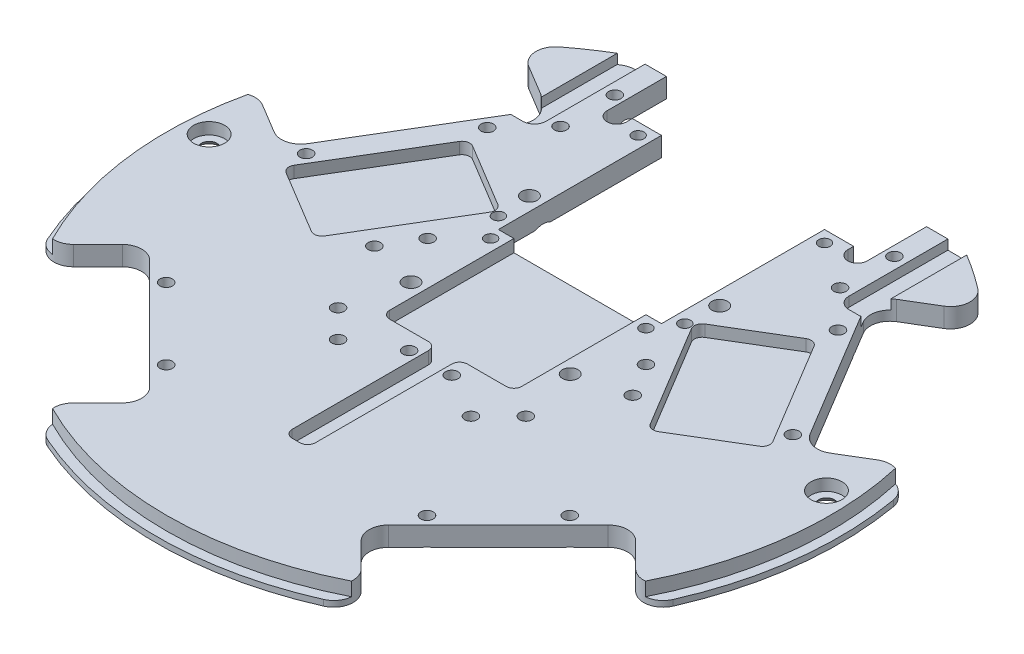
SolidWorks part; units mm, degrees
material "7079 Alloy"
ref_plane "Front" through (0, 0, 0) normal (0, 0, 1) x (1, 0, 0)
ref_plane "Top" through (0, 0, 0) normal (0, 1, 0) x (1, 0, 0)
ref_plane "Right" through (0, 0, 0) normal (1, 0, 0) x (0, 0, -1)
sketch "Sketch1" plane through (0, 0, 0) normal (0, 1, 0) x (1, 0, 0)
  line L0 (0, 0) -> (88, 0)
  line L1 (0, 88) -> (0, 0)
  line L2 (-88, 0) -> (0, 0)
  line L3 (0, -88) -> (0, 0)
  line L4 (0, 0) -> (62.2254, -62.2254)
  line L5 (0, 0) -> (-62.2254, -62.2254)
  line L6 (0, 0) -> (75.4307, 45.3234)
  line L7 (0, 0) -> (-75.4307, 45.3234)
  line L8 (59.4468, 64.8851) -> (41.5542, 54.1341)
  line L9 (41.5542, 54.1341) -> (67.3061, 11.2757)
  line L10 (67.3061, 11.2757) -> (85.1987, 22.0267)
  line L11 (77.3392, -41.9839) -> (62.579, -27.2236)
  line L12 (62.579, -27.2236) -> (27.2236, -62.579)
  line L13 (27.2236, -62.579) -> (41.9839, -77.3392)
  line L14 (-41.9839, -77.3392) -> (-27.2236, -62.579)
  line L15 (-27.2236, -62.579) -> (-62.579, -27.2236)
  line L16 (-62.579, -27.2236) -> (-77.3392, -41.9839)
  line L17 (-85.1987, 22.0267) -> (-67.3061, 11.2757)
  line L18 (-67.3061, 11.2757) -> (-41.5542, 54.1341)
  line L19 (-41.5542, 54.1341) -> (-59.4468, 64.8851)
  line L20 (-59.4468, 64.8851) -> (7.3885, 64.8851)
  line L21 (7.3885, 64.8851) -> (59.4468, 64.8851)
  line L22 (-41.5542, 54.1341) -> (0, 54.1341)
  line L23 (0, 54.1341) -> (41.5542, 54.1341)
  line L24 (41.5542, 54.1341) -> (41.5542, 77.5709)
  line L25 (-41.5542, 77.5709) -> (0, 77.5709)
  line L26 (-41.5542, 77.5709) -> (-41.5542, 54.1341)
  line L27 (0, 77.5709) -> (41.5542, 77.5709)
  circle A0 centre (0, 0) radius 88
  dimension "D1" = 176
  dimension "D2" = 31
  dimension "D3" = 31
  dimension "D4" = 45
  dimension "D5" = 24.5
  dimension "D6" = 24.5
  dimension "D7" = 24.5
  dimension "D8" = 24.5
  dimension "D9" = 25
  dimension "D10" = 25
  dimension "D11" = 25
  dimension "D12" = 25
  dimension "D13" = 25
  dimension "D14" = 25
  dimension "D15" = 25
  dimension "D16" = 25
sketch "Sketch2" plane through (0, 0, 0) normal (0, 1, 0) x (1, 0, 0)
  line L0 (85.1987, 22.0267) -> (67.3061, 11.2757)
  line L1 (67.3061, 11.2757) -> (41.5542, 54.1341)
  line L2 (77.3392, -41.9839) -> (62.579, -27.2236)
  line L3 (62.579, -27.2236) -> (27.2236, -62.579)
  line L4 (27.2236, -62.579) -> (41.9839, -77.3392)
  line L5 (-41.9839, -77.3392) -> (-27.2236, -62.579)
  line L6 (-27.2236, -62.579) -> (-62.579, -27.2236)
  line L7 (-62.579, -27.2236) -> (-77.3392, -41.9839)
  line L8 (-85.1987, 22.0267) -> (-67.3061, 11.2757)
  line L9 (-67.3061, 11.2757) -> (-41.5542, 54.1341)
  line L10 (-43, 76.7789) -> (43, 76.7789)
  line L15 (-41.5542, 54.1341) -> (-59.4468, 64.8851)
  line L16 (0, 0) -> (0, 111.6496) construction
  line L17 (41.5542, 54.1341) -> (59.4468, 64.8851)
  line L18 (-43, 76.7789) -> (43, 76.7789) construction
  arc A0 (85.1987, 22.0267) -> (77.3392, -41.9839) centre (0, 0) cw
  arc A1 (41.9839, -77.3392) -> (-41.9839, -77.3392) centre (0, 0) cw
  arc A2 (-77.3392, -41.9839) -> (-85.1987, 22.0267) centre (0, 0) cw
  arc A3 (-43, 76.7789) -> (-59.4468, 64.8851) centre (0, 0) ccw
  arc A4 (59.4468, 64.8851) -> (43, 76.7789) centre (0, 0) ccw
  dimension "D2" = 86
extrude "Extrude1" add sketch "Sketch2" against normal blind 5
sketch "Sketch3" plane through (0, 0, 0) normal (0, 1, 0) x (1, 0, 0)
  line L0 (-21, 76.7789) -> (-21, 21)
  line L1 (-21, 21) -> (21, 21)
  line L2 (21, 21) -> (21, 76.7789)
  line L3 (43, 76.7789) -> (-43, 76.7789) construction
  line L5 (-21, 76.7789) -> (21, 76.7789)
  dimension "D1" = 21
  dimension "D2" = 21
  dimension "D3" = 21
extrude "Extrude2" cut sketch "Sketch3" against normal up to surface (5 mm away) up to face at (0, -5, -1.5971)
sketch "Sketch4" plane through (0, 0, 0) normal (0, 1, 0) x (-1, 0, 0)
  line L0 (17, 13) -> (17, -27)
  line L1 (-3, 13) -> (-3, 52.119)
  line L2 (17, 13) -> (3, 13)
  line L3 (17, -27) -> (-17, -27)
  line L4 (-17, -27) -> (-17, 13)
  line L5 (21, -21) -> (-21, -21) construction
  line L6 (-3, 52.119) -> (3, 52.119)
  line L7 (3, 52.119) -> (3, 13)
  line L9 (-3, 13) -> (-17, 13)
  dimension "D1" = 34
  dimension "D2" = 17
  dimension "D3" = 34
  dimension "D4" = 40
  dimension "D5" = 6
  dimension "D6" = 14
extrude "Extrude3" cut sketch "Sketch4" against normal blind 3.2
sketch "Sketch5" plane through (0, 0, 0) normal (0, 1, 0) x (1, 0, 0)
  line L0 (42.9633, -4.5175) -> (62.6781, 7.3283)
  line L1 (62.6781, 7.3283) -> (44.6518, 37.3292)
  line L2 (44.6518, 37.3292) -> (24.9369, 25.4833)
  line L3 (24.9369, 25.4833) -> (42.9633, -4.5175)
  line L5 (67.3061, 11.2757) -> (41.5542, 54.1341) construction
  line L6 (85.1987, 22.0267) -> (67.3061, 11.2757) construction
  dimension "D1" = 6
  dimension "D2" = 35
  dimension "D3" = 23
  dimension "D4" = 1
extrude "Extrude4" cut sketch "Sketch5" against normal blind 3
mirror "Mirror1" about plane through (0, 0, 0) normal (1, 0, 0) of "Extrude4"
sketch "Sketch6" plane through (0, 0, 0) normal (0, 1, 0) x (1, 0, 0)
  line L0 (0, 0) -> (75.4307, 45.3234) construction
  line L1 (41.5542, 54.1341) -> (67.3061, 11.2757) construction
  line L2 (62.579, -27.2236) -> (27.2236, -62.579) construction
  line L3 (0, 0) -> (62.2254, -62.2254) construction
  circle A0 centre (45.1631, 42.303) radius 1.6
  circle A1 centre (62.6744, 13.1593) radius 1.6
  circle A2 centre (51.9723, -33.5876) radius 1.6
  circle A3 centre (33.5876, -51.9723) radius 1.6
  dimension "D1" = 3.2
  dimension "D2" = 3.2
  dimension "D3" = 3.2
  dimension "D4" = 3.2
  dimension "D6" = 3
  dimension "D8" = 3
  dimension "D9" = 3
  dimension "D10" = 13
  dimension "D11" = 13
  dimension "D12" = 3
  dimension "D5" = 13
  dimension "D7" = 21
extrude "Extrude5" cut sketch "Sketch6" against normal up to surface (5 mm away) up to face at (0, -5, -10.1957)
mirror "Mirror2" about plane through (0, 0, 0) normal (1, 0, 0) of "Extrude5"
sketch "Sketch7" plane through (0, 0, 0) normal (0, 1, 0) x (-1, 0, 0)
  line L1 (-21, -21) -> (-21, -76.7789) construction
  line L2 (-17, -21) -> (-21, -21) construction
  circle A0 centre (-24, -60) radius 1.5
  circle A1 centre (-24, -24) radius 1.5
  dimension "D2" = 3
  dimension "D3" = 3
  dimension "D4" = 3
  dimension "D5" = 3
  dimension "D6" = 3
  dimension "D1" = 36
extrude "Extrude6" cut sketch "Sketch7" against normal up to surface (5 mm away) up to face at (-51.9723, -5, 31.9876)
mirror "Mirror3" about plane through (0, 0, 0) normal (1, 0, 0) of "Extrude6"
sketch "Sketch8" plane through (0, 0, 0) normal (0, 1, 0) x (1, 0, 0)
  line L0 (33.5, 68.7344) -> (33.5, 63)
  line L6 (33.5, 63) -> (21, 63)
  line L7 (21, 21) -> (21, 76.7789) construction
  line L8 (21, 63) -> (21, 76.7789)
  line L9 (21, 76.7789) -> (33.5, 76.7789)
  line L10 (43, 76.7789) -> (21, 76.7789) construction
  line L11 (33.5, 76.7789) -> (33.5, 68.7344)
  circle A0 centre (24, 60) radius 1.5 construction
  dimension "D4" = 3
extrude "Extrude7" cut sketch "Sketch8" against normal up to surface (5 mm away) up to face at (-24, -5, -61.5)
mirror "Mirror4" about plane through (0, 0, 0) normal (1, 0, 0) of "Extrude7"
sketch "Sketch9" plane through (0, 0, 0) normal (0, 1, 0) x (1, 0, 0)
  line L5 (33.5, 63) -> (33.5, 76.7789) construction
  circle A0 centre (36, 66) radius 1.6
  circle A1 centre (36, 52) radius 1.6
  dimension "D1" = 3.2
  dimension "D2" = 3.2
  dimension "D3" = 52
  dimension "D4" = 66
  dimension "D5" = 2.5
extrude "Extrude8" cut sketch "Sketch9" against normal up to surface (5 mm away) up to face at (-24, -5, -61.5)
mirror "Mirror5" about plane through (0, 0, 0) normal (1, 0, 0) of "Extrude8"
fillet "Fillet2" radius 2 14 edges at (-17, -1.6, 13) (-42.9633, -1.5, 4.5175) (-24.9369, -1.5, -25.4833) (-44.6518, -1.5, -37.3292) (-62.6781, -1.5, -7.3283) (42.9633, -1.5, 4.5175) (24.9369, -1.5, -25.4833) (44.6518, -1.5, -37.3292) (62.6781, -1.5, -7.3283) (-3, -1.6, 52.119) (3, -1.6, 52.119) (-3, -1.6, 13) (3, -1.6, 13) (17, -1.6, 13)
fillet "Fillet3" radius 5 16 edges at (59.4468, -2.5, -64.8851) (41.5542, -2.5, -54.1341) (67.3061, -2.5, -11.2757) (85.1987, -2.5, -22.0267) (77.3392, -2.5, 41.9839) (62.579, -2.5, 27.2236) (27.2236, -2.5, 62.579) (41.9839, -2.5, 77.3392) (-27.2236, -2.5, 62.579) (-41.9839, -2.5, 77.3392) (-62.579, -2.5, 27.2236) (-77.3392, -2.5, 41.9839) (-85.1987, -2.5, -22.0267) (-67.3061, -2.5, -11.2757) (-41.5542, -2.5, -54.1341) (-59.4468, -2.5, -64.8851)
fillet "Fillet4" radius 5 2 edges at (43, -2.5, -76.7789) (-43, -2.5, -76.7789)
sketch "Sketch11" plane through (0, 0, 0) normal (0, 1, 0) x (1, 0, 0)
  line L0 (-21, 63) -> (-33.5, 63) construction
  line L3 (-21, 21) -> (-21, 63) construction
  line L4 (21, 21) -> (21, 63) construction
  circle A2 centre (24.5, 32.5) radius 2
  circle A3 centre (-24.5, 32.5) radius 2
  dimension "D2" = 30.5
  dimension "D7" = 4
  dimension "D8" = 4
  dimension "D9" = 3.5
  dimension "D10" = 3.5
extrude "Extrude10" cut sketch "Sketch11" against normal up to surface (5 mm away) up to face at (-36, -5, -67.6)
sketch "Sketch14" plane through (0, 0, 0) normal (0, 1, 0) x (1, 0, 0)
  line L3 (17.112, -24.1831) -> (24.1831, -17.112) construction
  line L4 (33.9018, -69.2571) -> (69.2571, -33.9018) construction
  line L8 (37.0444, -72.3997) -> (30.7591, -66.1145) construction
  line L9 (66.1145, -30.7591) -> (72.3997, -37.0444) construction
  line L10 (62.6744, 13.1593) -> (45.1631, 42.303) construction
  line L11 (49.6495, 58.9983) -> (75.4014, 16.1399) construction
  line L12 (45.84, 56.7093) -> (53.4591, 61.2873) construction
  line L13 (79.211, 18.4289) -> (71.5919, 13.8509) construction
  line L14 (33.5876, -51.9723) -> (51.9723, -33.5876) construction
  circle A2 centre (24.1831, -17.112) radius 1.6
  circle A3 centre (17.112, -24.1831) radius 1.6
  circle A4 centre (28.1195, 9.8961) radius 1.6
  circle A5 centre (33.2699, 1.3244) radius 1.6
  point P28 (20.6475, -20.6475)
  dimension "D3" = 3.2
  dimension "D4" = 31.3
  dimension "D7" = 31.3
  dimension "D9" = 3.2
  dimension "D10" = 31.3
  dimension "D12" = 10
  dimension "D8" = 3.2
  dimension "D14" = 3.2
  dimension "D2" = 10
  dimension "D5" = 31.3
  dimension "D6" = 19
  dimension "D13" = 25
sketch "Sketch20" plane through (0, 0, 0) normal (0, 1, 0) x (1, 0, 0)
  circle A0 centre (20.5, -2) radius 2
  circle A1 centre (-20.5, -2) radius 2
  dimension "D1" = 4
  dimension "D2" = 4
  dimension "D3" = 20.5
  dimension "D4" = 20.5
  dimension "D5" = 2
  dimension "D6" = 2
extrude "Extrude19" cut sketch "Sketch20" against normal up to surface (5 mm away) up to face at (-24.5, -5, -34.5)
sketch "Sketch27" plane through (0, 0, 0) normal (0, 1, 0) x (1, 0, 0)
  line L1 (17, 21) -> (21, 21) construction
  line L2 (17, -11) -> (17, 21) construction
  line L3 (-17, 21) -> (-17, -11) construction
  circle A0 centre (20, 18) radius 1.5
  circle A1 centre (-20, 18) radius 1.5
  dimension "D1" = 3
  dimension "D2" = 3
  dimension "D4" = 3
  dimension "D3" = 3
  dimension "D5" = 3
extrude "Extrude26" cut sketch "Sketch27" against normal up to surface (5 mm away) up to face at (-20.5, -5, 0)
sketch "Sketch29" plane through (0, 0, 0) normal (0, 1, 0) x (1, 0, 0)
  circle A0 centre (-79.5, 5) radius 4
  circle A1 centre (79.5, 5) radius 4
  dimension "D2" = 79.5
  dimension "D4" = 8
  dimension "D5" = 8
  dimension "D1" = 5
  dimension "D3" = 79.5
extrude "Extrude28" cut sketch "Sketch29" against normal blind 3
sketch "Sketch30" plane through (0, -3, 0) normal (0, 1, 0) x (1, 0, 0)
  circle A0 centre (79.5, 5) radius 2
  circle A1 centre (-79.5, 5) radius 2
  dimension "D1" = 4
  dimension "D2" = 4
extrude "Extrude29" cut sketch "Sketch30" against normal up to surface (2 mm away) up to face at (-20, -5, -19.5)
extrude "Extrude30" cut sketch "Sketch14" against normal up to surface (5 mm away) up to face at (-79.5, -5, -7)
mirror "Mirror9" about plane through (0, 0, 0) normal (1, 0, 0) of "Extrude30"
sketch "Sketch31" plane through (0, 0, 0) normal (0, 1, 0) x (1, 0, 0)
  line L0 (-74.1867, 42.5039) -> (-76.3559, 43.7467)
  line L2 (74.1867, 42.5039) -> (76.3559, 43.7467)
  arc A0 (-74.1867, 42.5039) -> (74.1867, 42.5039) centre (0, 0) ccw
  arc A1 (-76.3559, 43.7467) -> (76.3559, 43.7467) centre (0, 0) ccw
  dimension "D1" = 171
extrude "Cut-Extrude1" cut sketch "Sketch31" against normal blind 3.5
sketch "Sketch33" plane through (0, 0, 0) normal (0, 1, 0) x (1, 0, 0)
  line L0 (-39, 76.7789) -> (-45, 76.7789)
  line L3 (-33.5, 76.7789) -> (-41.6748, 76.7789) construction
  line L4 (-45, 76.7789) -> (-45, 48.2789)
  line L9 (-45, 48.2789) -> (-39, 48.2789)
  line L10 (-39, 48.2789) -> (-39, 76.7789)
  line L11 (0, 0) -> (0, 104.2822) construction
  line L12 (39, 48.2789) -> (39, 76.7789)
  line L13 (45, 48.2789) -> (39, 48.2789)
  line L14 (45, 76.7789) -> (45, 48.2789)
  line L15 (39, 76.7789) -> (45, 76.7789)
  dimension "D1" = 5.5
  dimension "D2" = 6
  dimension "D3" = 28.5
extrude "Cut-Extrude3" cut sketch "Sketch33" against normal blind 2.5
fillet "Fillet5" radius 3 2 edges at (39, -1.25, -48.2789) (-39, -1.25, -48.2789)
sketch "Sketch34" plane through (0, 0, 0) normal (0, 1, 0) x (1, 0, 0)
  line L0 (-33.5, 63) -> (-33.5, 59)
  line L1 (-33.5, 59) -> (-28.5, 59)
  line L2 (-28.5, 59) -> (-28.5, 63)
  line L4 (-21, 63) -> (-33.5, 63) construction
  line L5 (-28.5, 63) -> (-33.5, 63)
  line L6 (0, 0) -> (0, 90.7879) construction
  line L7 (28.5, 63) -> (33.5, 63)
  line L8 (28.5, 59) -> (28.5, 63)
  line L9 (33.5, 59) -> (28.5, 59)
  line L10 (33.5, 63) -> (33.5, 59)
  dimension "D1" = 4
  dimension "D2" = 5
extrude "Cut-Extrude4" cut sketch "Sketch34" against normal blind 10
fillet "Fillet6" radius 2.5 4 edges at (28.5, -2.5, -59) (33.5, -2.5, -59) (-28.5, -2.5, -59) (-33.5, -2.5, -59)
sketch "Sketch37" plane through (0, 0, 0) normal (0, 1, 0) x (1, 0, 0)
  line L1 (-5.5, -17.5) -> (5.5, -17.5) construction
  line L2 (-24.5, 32.5) -> (24.5, 32.5) construction
  line L3 (0, 0) -> (0, -85.5) construction
  circle A0 centre (-5.5, -17.5) radius 1.6
  circle A1 centre (5.5, -17.5) radius 1.6
  arc A5 (-38.492, -76.3454) -> (38.492, -76.3454) centre (0, 0) ccw construction
  dimension "D1" = 3.2
  dimension "D2" = 3.2
  dimension "D3" = 11
  dimension "D4" = 50
  dimension "D5" = 5.5
extrude "Cut-Extrude7" cut sketch "Sketch37" against normal blind 10
chamfer "Chamfer1" distance 1.5 angle 45 28 edges at (-5.5, -5, 15.9) (5.5, -5, 15.9) (-36, -5, -53.6) (-36, -5, -67.6) (-24, -5, -61.5) (36, -5, -53.6) (36, -5, -67.6) (24, -5, -61.5) (-24, -5, -25.5) (24, -5, -25.5) (-20, -5, -19.5) (20, -5, -19.5) (-33.2699, -5, -2.9244) (-24.1831, -5, 15.512) (-17.112, -5, 22.5831) (17.112, -5, 22.5831) (28.1195, -5, -11.4961) (33.2699, -5, -2.9244) (-45.1631, -5, -43.903) (-62.6744, -5, -14.7593) (45.1631, -5, -43.903) (62.6744, -5, -14.7593) (51.9723, -5, 31.9876) (33.5876, -5, 50.3723) (-33.5876, -5, 50.3723) (-51.9723, -5, 31.9876) (-28.1195, -5, -11.4961) (24.1831, -5, 15.512)
chamfer "Chamfer2" distance 2 angle 45 6 edges at (-20.5, -5, 0) (20.5, -5, 0) (-79.5, -5, -7) (-24.5, -5, -34.5) (24.5, -5, -34.5) (79.5, -5, -7)
sketch "Sketch38" plane through (0, -3.2, 0) normal (0, 1, 0) x (1, 0, 0)
  line L0 (3, -50.119) -> (3, -15) construction
  circle A0 centre (0, -49) radius 1.075
  dimension "D3" = 2.15
  dimension "D1" = 49
  dimension "D2" = 3
extrude "Cut-Extrude8" cut sketch "Sketch38" against normal blind 10
